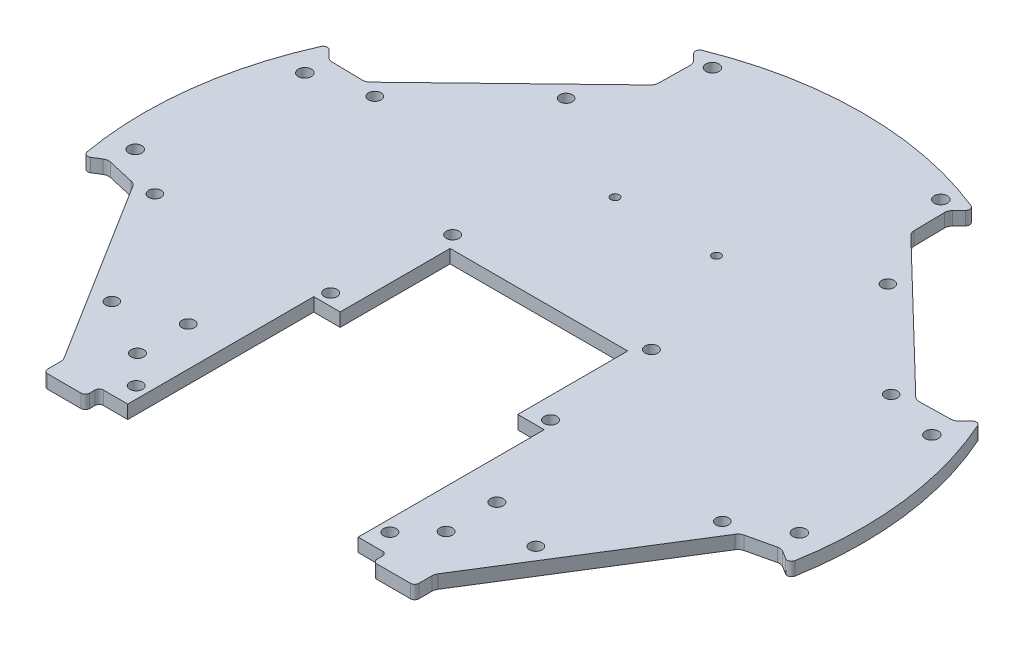
SolidWorks part; units mm, degrees
note: '?' marks a value the reader was unsure of.
material "6061 Alloy"
ref_plane "Front Plane" through (0, 0, 0) normal (0, 0, 1) x (1, 0, 0)
ref_plane "Top Plane" through (0, 0, 0) normal (0, 1, 0) x (1, 0, 0)
ref_plane "Right Plane" through (0, 0, 0) normal (1, 0, 0) x (0, 0, -1)
sketch "Sketch1" plane through (0, 0, 0) normal (0, 1, 0) x (1, 0, 0)
  line L0 (0, 0) -> (0, -62.55) construction
  line L1 (-83.4462, -16.178) -> (-71.2857, -8.5793) construction
  line L6 (0, 0) -> (-59.046, 61.1439) construction
  line L7 (0, 0) -> (-72.0841, -45.0431) construction
  line L8 (-33.174, 78.2591) -> (-23.2129, 67.9442) construction
  line L9 (-72.0841, -45.0431) -> (-70.388, -43.9833) construction
  line L10 (-70.388, -43.9833) -> (-84.9608, -20.662) construction
  line L11 (-84.9608, -20.662) -> (-72.2401, -12.7132) construction
  line L12 (-72.2401, -12.7132) -> (-43.0945, -59.3558) construction
  line L13 (-43.0945, -59.3558) -> (-55.8152, -67.3046) construction
  line L14 (-55.8152, -67.3046) -> (-70.388, -43.9833) construction
  line L21 (-59.046, 61.1439) -> (-57.6566, 59.7052)
  line L22 (-77.4385, 40.6021) -> (-37.8748, 78.8083) construction
  line L23 (-73.9694, 32.6911) -> (-77.0537, 35.885)
  line L24 (-37.8748, 78.8083) -> (-27.4549, 68.0182) construction
  line L25 (-27.4549, 68.0182) -> (-67.0186, 29.812) construction
  line L26 (-67.0186, 29.812) -> (-77.4385, 40.6021) construction
  line L27 (-43.0945, -64.8266) -> (-34, -64.8266)
  line L33 (-86.5505, -18.1178) -> (-71.2857, -8.5793) construction
  line L34 (0, 0) -> (0, 50000) construction
  line L35 (0, 0) -> (-50000, 0) construction
  line L36 (-57.5543, -62.55) -> (-19.8595, -62.55) construction
  line L38 (-67.0927, 25.57) -> (-79.5965, 38.5181) construction
  line L39 (-54.9774, -64.8266) -> (0, -64.8266) construction
  line L40 (-35.7168, 80.8923) -> (-23.2129, 67.9442) construction
  line L41 (-38.9606, -60.3102) -> (-54.2255, -69.8488) construction
  line L42 (-34, -62.55) -> (-19.8595, -62.55) construction
  line L43 (-43.0945, -64.8266) -> (-43.0945, -58.4123) construction
  line L45 (73.9694, 32.6911) -> (77.0537, 35.885)
  line L46 (-71.2857, -8.5793) -> (-38.9606, -60.3102) construction
  line L47 (83.4462, -16.178) -> (79.6809, -13.8252)
  line L48 (69.4846, -16.1792) -> (43.8945, -57.132)
  line L50 (43.0945, -64.8266) -> (34, -64.8266)
  line L51 (34, -62.55) -> (34, -64.8266)
  line L52 (0, 0) -> (72.0841, -45.0431) construction
  line L53 (0, 0) -> (59.046, 61.1439) construction
  line L54 (-30.0897, 75.0653) -> (-30.2847, 63.8954)
  line L55 (-62.7996, 32.4961) -> (-30.2847, 63.8954)
  line L56 (-30.0897, 75.0653) -> (-33.174, 78.2591)
  line L57 (73.9694, 32.6911) -> (77.0537, 35.885)
  line L58 (30.0897, 75.0653) -> (33.174, 78.2591)
  line L59 (-34, -62.55) -> (-34, -61.55)
  line L60 (62.7996, 32.4961) -> (30.2847, 63.8954)
  line L61 (-73.9694, 32.6911) -> (-62.7996, 32.4961)
  line L62 (-77.0537, 35.885) -> (-67.0927, 25.57) construction
  line L63 (-83.4462, -16.178) -> (-79.6809, -13.8252)
  line L64 (-79.6809, -13.8252) -> (-69.4846, -16.1792)
  line L65 (-69.4846, -16.1792) -> (-43.8945, -57.132)
  line L66 (-27.4549, 68.0182) -> (-23.2129, 67.9442) construction
  line L67 (-72.2401, -12.7132) -> (-71.2857, -8.5793) construction
  line L68 (30.0897, 75.0653) -> (30.2847, 63.8954)
  line L69 (73.9694, 32.6911) -> (62.7996, 32.4961)
  line L70 (-34, -62.55) -> (-34, -64.8266)
  line L71 (79.6809, -13.8252) -> (69.4846, -16.1792)
  line L72 (-34, -61.55) -> (-20, -61.55)
  line L73 (-20, -61.55) -> (-19.8595, -62.55)
  line L74 (-19.8595, -62.55) -> (19.8595, -62.55)
  line L75 (20, -61.55) -> (19.8595, -62.55)
  line L76 (34, -61.55) -> (20, -61.55)
  line L77 (34, -62.55) -> (34, -61.55)
  line L78 (-43.0945, -64.8266) -> (-43.8945, -64.8266)
  line L79 (-19.8595, -62.55) -> (0, -62.55) construction
  line L80 (-19.8595, -62.55) -> (34, -62.55) construction
  line L81 (-43.8945, -64.8266) -> (-43.8945, -57.132)
  line L82 (-43.0945, -58.4123) -> (-43.8945, -57.132) construction
  line L83 (43.8945, -64.8266) -> (43.8945, -57.132)
  line L84 (43.0945, -64.8266) -> (43.8945, -64.8266)
  line L97 (-23.2129, 67.9442) -> (-67.0927, 25.57) construction
  circle A0 centre (0, 0) radius 85 construction
  circle A1 centre (0, 0) radius 90 construction
  arc A51 (-77.0537, 35.885) -> (-83.4462, -16.178) centre (0, 0) ccw
  arc A52 (77.0537, 35.885) -> (83.4462, -16.178) centre (0, 0) cw
  arc A54 (-33.174, 78.2591) -> (33.174, 78.2591) centre (0, 0) cw
  point P29 (-31.6318, 76.6622)
  point P33 (-47.2368, 48.9151)
  point P34 (31.6318, 76.6622)
  point P35 (-57.6673, -36.0345)
  point P85 (-57.6566, 59.7052)
  dimension "D2" = 58
  dimension "D10" = 82
  dimension "D12" = 170
  dimension "D14" = 34
  dimension "D13" = 1
  dimension "D15" = 3
  dimension "D3" = 180
  dimension "D4" = 64.8266
  dimension "D5" = 44
  dimension "D6" = 15
  dimension "D7" = 55
  dimension "D8" = 62.55
  dimension "D9" = 2
  dimension "D11" = 2
  dimension "D16" = 7
  dimension "D17" = 7
  dimension "D18" = 0.5
  dimension "D19" = 1
  dimension "D20" = 14
  dimension "D21" = 0.8
extrude "Boss-Extrude4" add sketch "Sketch1" along normal mid plane 3.175
ref_point "Rear_Axle_Center (L)"
ref_axis "Rear_Axle_Proj (L)" through (46.5421, 0, -48.1958) along (0, 1, 0)?
ref_point "Front_Axle_Center (L)"
ref_axis "Front_Axle_Proj (L)" through (57.2432, 0, 35.7696) along (0, 1, 0)?
ref_point "Front_Axle_Center (R)"
ref_axis "Front_Axle_Proj (R)" through (-57.2432, 0, 35.7696) along (0, 1, 0)?
ref_point "Read_Axle_Center (R)"
ref_axis "Rear_Axle_Proj (R)" through (-46.5421, 0, -48.1958) along (0, 1, 0)?
sketch "Sketch17" plane through (0, 1.5875, 0) normal (0, 1, 0) x (1, 0, 0)
  line L0 (0, -57.55) -> (0, -62.55) construction
  line L1 (-19.8595, -62.55) -> (19.8595, -62.55) construction
  circle A0 centre (0, -57.55) radius 8.5
  dimension "D1" = 17
  dimension "D2" = 5
extrude "Boss-Extrude5" [suppressed] add sketch "Sketch17" against normal up to surface (3.175 mm away)
ref_plane "Plane1" through (0, 0, 10) normal (0, 0, 1) x (1, 0, 0)
hole_wizard "M3 Clearance Hole3" positions "Sketch18" profile "Sketch19" hole size "M3" standard "ANSI Metric" end condition through all
sketch "Sketch18" plane through (0, -1.5875, 0) normal (0, -1, 0) x (-1, 0, 0)
  line L0 (-36.5, -50) -> (-36.5, -38) construction
  line L3 (0, 0) -> (0, -38) construction
  line L4 (36.5, -50) -> (36.5, -38) construction
  line L6 (0, -38) -> (36.5, -38) construction
  line L8 (0, -38) -> (-36.5, -38) construction
  line L9 (-36.5, -44) -> (36.5, -44) construction
  line L10 (0, -44) -> (0, 0) construction
  point P1 (36.5, -50)
  point P3 (36.5, -38)
  point P5 (-36.5, -50)
  point P33 (-36.5, -38)
  dimension "D1" = 12
  dimension "D2" = 73
  dimension "D4" = 38
sketch "Sketch19" plane through (-36.5, -1.5875, 50) normal (1, 0, 0) x (0, 0, -1)
  line L0 (0, 0) -> (0, 3.175)
  line L1 (0, 3.175) -> (1.5, 3.175)
  line L2 (1.5, 3.175) -> (1.5, 0)
  line L5 (1.5, 0) -> (0, 0)
  line L11 (0, -6.35) -> (0, 107.95) construction
  dimension "Thru Hole Dia." = 3
  dimension "Thru Hole Depth" = 3.175
hole_wizard "M3 Clearance Hole1" positions "Sketch11" profile "Sketch12" hole size "M3" standard "ANSI Metric" end condition through all
sketch "Sketch11" plane through (0, 1.5875, 0) normal (0, 1, 0) x (1, 0, 0)
  line L0 (83.4462, -16.178) -> (79.6809, -13.8252) construction
  line L2 (73.9694, 32.6911) -> (77.0537, 35.885) construction
  line L4 (-73.9694, 32.6911) -> (-77.0537, 35.885) construction
  line L6 (0, 0) -> (0, -50000) construction
  line L7 (78.4111, 9.6277) -> (84.3664, 10.3589) construction
  line L10 (74.155, 27.2403) -> (78.5423, -8.4914) construction
  line L12 (78.4111, 9.6277) -> (76.3487, 9.3744) construction
  arc A7 (77.964, -12.7523) -> (72.563, 31.2347) centre (0, 0) ccw construction
  arc A13 (-77.964, -12.7523) -> (-72.563, 31.2347) centre (0, 0) cw construction
  arc A17 (83.4462, -16.178) -> (77.0537, 35.885) centre (0, 0) ccw construction
  point P34 (78.5423, -8.4914)
  point P66 (74.155, 27.2403)
  point P70 (-74.155, 27.2403)
  point P71 (-78.5423, -8.4914)
  dimension "D1" = 6
  dimension "D2" = 36
sketch "Sketch12" plane through (-78.5423, 1.5875, 8.4914) normal (1, 0, 0) x (0, 0, 1)
  line L0 (0, 0) -> (0, 3.175)
  line L1 (0, 3.175) -> (1.55, 3.175)
  line L2 (1.55, 3.175) -> (1.55, 0)
  line L5 (1.55, 0) -> (0, 0)
  line L11 (0, -6.35) -> (0, 107.95) construction
  dimension "Thru Hole Dia." = 3.1
  dimension "Thru Hole Depth" = 3.175
hole_wizard "M3 Clearance Hole4" positions "Sketch9" profile "Sketch10" hole size "M3" standard "ANSI Metric" end condition through all
sketch "Sketch9" plane through (0, -1.5875, 0) normal (0, -1, 0) x (-1, 0, 0)
  line L0 (0, 0) -> (0, 63.4318) construction
  line L1 (-38.0437, 52.9272) -> (38.0437, 52.9272) construction
  line L3 (61.0625, 30.6981) -> (-61.0625, 30.6981) construction
  line L4 (-67.0993, -15.2789) -> (67.0993, -15.2789) construction
  line L5 (50.1419, -42.4164) -> (-50.1419, -42.4164) construction
  line L6 (-61.0625, 30.6981) -> (-38.0437, 52.9272) construction
  line L7 (38.0437, 52.9272) -> (61.0625, 30.6981) construction
  line L8 (67.0993, -15.2789) -> (50.1419, -42.4164) construction
  line L9 (-50.1419, -42.4164) -> (-67.0993, -15.2789) construction
  line L10 (0, 0) -> (-44.8055, 46.3974) construction
  line L11 (0, 0) -> (44.8055, 46.3974) construction
  line L12 (0, 0) -> (-96.9468, 0) construction
  line L14 (-55.1231, -34.4448) -> (0, 0) construction
  line L15 (0, 0) -> (55.1231, -34.4448) construction
  line L18 (-69.4846, -16.1792) -> (-43.8945, -57.132) construction
  line L19 (-62.7996, 32.4961) -> (-30.2847, 63.8954) construction
  point P0 (-67.0993, -15.2789)
  point P2 (-50.1419, -42.4164)
  point P9 (-61.0625, 30.6981)
  point P11 (-38.0437, 52.9272)
  point P30 (50.1419, -42.4164)
  point P31 (67.0993, -15.2789)
  point P32 (38.0437, 52.9272)
  point P33 (61.0625, 30.6981)
  dimension "D9" = 46
  dimension "D10" = 46
  dimension "D11" = 32
  dimension "D12" = 32
  dimension "D7" = 58
  dimension "D5" = 32
  dimension "D6" = 2.5
  dimension "D8" = 9.4
  dimension "D2" = 44
  dimension "D3" = 32
  dimension "D4" = 2.5
  dimension "D13" = 9.4
sketch "Sketch10" plane through (67.0993, -1.5875, 15.2789) normal (1, 0, 0) x (0, 0, -1)
  line L0 (0, 0) -> (0, 3.175)
  line L1 (0, 3.175) -> (1.475, 3.175)
  line L2 (1.475, 3.175) -> (1.475, 0)
  line L5 (1.475, 0) -> (0, 0)
  line L11 (0, -6.35) -> (0, 107.95) construction
  dimension "Thru Hole Dia." = 2.95
  dimension "Thru Hole Depth" = 3.175
hole_wizard "M3 Clearance Hole2" positions "Sketch13" profile "Sketch14" hole size "M3" standard "ANSI Metric" end condition through all
sketch "Sketch13" plane through (0, 1.5875, 0) normal (0, 1, 0) x (1, 0, 0)
  line L0 (0, 0) -> (0, 85) construction
  line L2 (-24, 47) -> (-24, 81) construction
  line L3 (-24, 47) -> (24, 47) construction
  line L4 (-24, 81) -> (24, 81) construction
  line L5 (24, 47) -> (24, 81) construction
  line L6 (-24, 47) -> (24, 81) construction
  line L7 (-24, 81) -> (24, 47) construction
  line L8 (-38.0437, 52.9272) -> (-61.0625, 30.6981) construction
  line L10 (-36.307, 51.1289) -> (-59.3259, 28.8998) construction
  line L11 (-16.3488, 39.8187) -> (-31.6313, 55.6441) construction
  line L12 (-16.3488, 39.8187) -> (-48.7191, 8.559) construction
  line L13 (-31.6313, 55.6441) -> (-64.0016, 24.3845) construction
  line L14 (-48.7191, 8.559) -> (-64.0016, 24.3845) construction
  line L15 (-16.3488, 39.8187) -> (-64.0016, 24.3845) construction
  line L16 (-31.6313, 55.6441) -> (-48.7191, 8.559) construction
  line L17 (-49.5531, 41.8127) -> (-40.1752, 32.1016) construction
  line L18 (-27, 76.4978) -> (-27, 80.5978) construction
  arc A0 (33.174, 78.2591) -> (-33.174, 78.2591) centre (0, 0) ccw construction
  circle A1 centre (-16.2162, 44) radius 3 construction
  circle A2 centre (-27, 76.4978) radius 3 construction
  point P65 (0, 64)
  point P181 (-27, 76.4978)
  point P184 (27, 76.4978)
  dimension "D7" = 6
  dimension "D1" = 48
  dimension "D2" = 34
  dimension "D3" = 4
  dimension "D5" = 45
  dimension "D6" = 22
  dimension "D8" = 4.1
  dimension "D4" = 2.5
sketch "Sketch14" plane through (27, 1.5875, -76.4978) normal (1, 0, 0) x (0, 0, 1)
  line L0 (0, 0) -> (0, 3.175)
  line L1 (0, 3.175) -> (1.55, 3.175)
  line L2 (1.55, 3.175) -> (1.55, 0)
  line L5 (1.55, 0) -> (0, 0)
  line L11 (0, -6.35) -> (0, 107.95) construction
  dimension "Thru Hole Dia." = 3.1
  dimension "Thru Hole Depth" = 3.175
hole_wizard "M3 Clearance Hole5" [suppressed] positions "Sketch24" profile "Sketch25" hole size "M3" standard "ANSI Metric"
sketch "Sketch24" plane through (0, 1.5875, 0) normal (0, 1, 0) x (1, 0, 0)
  line L1 (-11, -4.4) -> (11, -4.4) construction
  line L2 (11, -4.4) -> (11, -36.4) construction
  line L3 (11, -36.4) -> (-11, -36.4) construction
  line L4 (-11, -36.4) -> (-11, -4.4) construction
  line L7 (-11, 37.6) -> (11, 37.6) construction
  line L8 (0, -4.4) -> (0, 0) construction
  line L9 (0, 0) -> (0, 37.6) construction
  point P8 (-11, -4.4)
  point P10 (11, -4.4)
  point P12 (11, -36.4)
  point P14 (-11, -36.4)
  point P42 (-11, 37.6)
  point P45 (11, 37.6)
  dimension "D1" = 22
  dimension "D2" = 32
  dimension "D3" = 4.4
  dimension "D4" = 42
sketch "Sketch25" plane through (-11, 1.5875, 4.4) normal (1, 0, 0) x (0, 0, 1)
  line L0 (0, 0) -> (0, 3.175)
  line L1 (0, 3.175) -> (1.5, 3.175)
  line L2 (1.5, 3.175) -> (1.5, 0)
  line L5 (1.5, 0) -> (0, 0)
  line L11 (0, -6.35) -> (0, 107.95) construction
  dimension "Thru Hole Dia." = 3
  dimension "Thru Hole Depth" = 3.175
sketch "Sketch20" plane through (0, 1.5875, 0) normal (0, 1, 0) x (1, 0, 0)
  line L0 (-16.1485, 44) -> (-16.1485, 39) construction
  line L1 (-14.6485, 44) -> (-14.6485, 39)
  line L2 (-17.6485, 44) -> (-17.6485, 39)
  line L3 (0, 0) -> (0, 85) construction
  line L5 (16.1485, 44) -> (16.1485, 39) construction
  line L6 (14.6485, 44) -> (14.6485, 39)
  line L7 (17.6485, 44) -> (17.6485, 39)
  arc A0 (-14.6485, 44) -> (-17.6485, 44) centre (-16.1485, 44) ccw
  arc A1 (-17.6485, 39) -> (-14.6485, 39) centre (-16.1485, 39) ccw
  arc A5 (33.174, 78.2591) -> (-33.174, 78.2591) centre (0, 0) ccw construction
  arc A7 (14.6485, 44) -> (17.6485, 44) centre (16.1485, 44) cw
  arc A8 (17.6485, 39) -> (14.6485, 39) centre (16.1485, 39) cw
  point P2 (-16.1485, 41.5)
  point P16 (16.1485, 41.5)
  dimension "D1" = 44
  dimension "D2" = 3
  dimension "D3" = 5
  dimension "D4" = 16.1485
extrude "Cut-Extrude1" [suppressed] cut sketch "Sketch20" against normal through all
sketch "Sketch22" plane through (0, 1.5875, 0) normal (0, 1, 0) x (1, 0, 0)
  line L0 (-56.6896, -36.6556) -> (-58.0464, -37.5035) construction
  line L1 (-69.4846, -16.1792) -> (-43.8945, -57.132) construction
  line L3 (30.2452, 66.1578) -> (65.062, 32.5356)
  line L4 (71.6894, -15.6702) -> (43.8945, -60.1514)
  line L5 (-19.8595, -62.55) -> (19.8595, -62.55) construction
  line L6 (-43.8945, -64.8266) -> (-43.8945, -57.132) construction
  line L28 (-30.2452, 66.1578) -> (-65.062, 32.5356)
  line L29 (-71.6894, -15.6702) -> (-43.8945, -60.1514)
  line L30 (-79.6809, -13.8252) -> (-69.4846, -16.1792) construction
  line L31 (0, 85) -> (0, -62.55) construction
  line L32 (-46.5421, 48.1958) -> (-47.6536, 49.3467) construction
  line L37 (-20, -61.55) -> (-19.8595, -62.55)
  line L38 (-20, -61.55) -> (-19.8595, -62.55)
  line L40 (-43.8945, -57.132) -> (-43.8945, -64.8266)
  line L41 (-43.8945, -57.132) -> (-43.8945, -64.8266)
  line L43 (43.8945, -64.8266) -> (43.8945, -57.132)
  line L44 (43.8945, -64.8266) -> (43.8945, -57.132)
  line L56 (-19.8595, -62.55) -> (19.8595, -62.55)
  line L58 (19.8595, -62.55) -> (20, -61.55)
  line L59 (20, -61.55) -> (34, -61.55)
  line L60 (34, -61.55) -> (34, -64.8266)
  line L61 (34, -64.8266) -> (43.8945, -64.8266)
  line L63 (43.8945, -57.132) -> (69.4846, -16.1792)
  line L64 (69.4846, -16.1792) -> (79.6809, -13.8252)
  line L65 (79.6809, -13.8252) -> (83.4462, -16.178)
  line L66 (77.0537, 35.885) -> (73.9694, 32.6911)
  line L67 (73.9694, 32.6911) -> (62.7996, 32.4961)
  line L68 (62.7996, 32.4961) -> (30.2847, 63.8954)
  line L69 (30.2847, 63.8954) -> (30.0897, 75.0653)
  line L70 (30.0897, 75.0653) -> (33.174, 78.2591)
  line L71 (-33.174, 78.2591) -> (-30.0897, 75.0653)
  line L72 (-30.0897, 75.0653) -> (-30.2847, 63.8954)
  line L73 (-30.2847, 63.8954) -> (-62.7996, 32.4961)
  line L74 (-62.7996, 32.4961) -> (-73.9694, 32.6911)
  line L75 (-73.9694, 32.6911) -> (-77.0537, 35.885)
  line L76 (-83.4462, -16.178) -> (-79.6809, -13.8252)
  line L77 (-79.6809, -13.8252) -> (-69.4846, -16.1792)
  line L78 (-69.4846, -16.1792) -> (-43.8945, -57.132)
  line L80 (-43.8945, -64.8266) -> (-34, -64.8266)
  line L81 (-34, -64.8266) -> (-34, -61.55)
  line L82 (-34, -61.55) -> (-20, -61.55)
  line L84 (-19.8595, -62.55) -> (19.8595, -62.55)
  line L86 (19.8595, -62.55) -> (20, -61.55)
  line L87 (20, -61.55) -> (34, -61.55)
  line L88 (34, -61.55) -> (34, -64.8266)
  line L89 (34, -64.8266) -> (43.8945, -64.8266)
  line L91 (43.8945, -57.132) -> (69.4846, -16.1792)
  line L92 (69.4846, -16.1792) -> (79.6809, -13.8252)
  line L93 (79.6809, -13.8252) -> (83.4462, -16.178)
  line L94 (77.0537, 35.885) -> (73.9694, 32.6911)
  line L95 (73.9694, 32.6911) -> (62.7996, 32.4961)
  line L96 (62.7996, 32.4961) -> (30.2847, 63.8954)
  line L97 (30.2847, 63.8954) -> (30.0897, 75.0653)
  line L98 (30.0897, 75.0653) -> (33.174, 78.2591)
  line L99 (-33.174, 78.2591) -> (-30.0897, 75.0653)
  line L100 (-30.0897, 75.0653) -> (-30.2847, 63.8954)
  line L101 (-30.2847, 63.8954) -> (-62.7996, 32.4961)
  line L102 (-62.7996, 32.4961) -> (-73.9694, 32.6911)
  line L103 (-73.9694, 32.6911) -> (-77.0537, 35.885)
  line L104 (-83.4462, -16.178) -> (-79.6809, -13.8252)
  line L105 (-79.6809, -13.8252) -> (-69.4846, -16.1792)
  line L106 (-69.4846, -16.1792) -> (-43.8945, -57.132)
  line L108 (-43.8945, -64.8266) -> (-34, -64.8266)
  line L109 (-34, -64.8266) -> (-34, -61.55)
  line L110 (-34, -61.55) -> (-20, -61.55)
  arc A9 (83.4462, -16.178) -> (77.0537, 35.885) centre (0, 0) ccw
  arc A10 (33.174, 78.2591) -> (-33.174, 78.2591) centre (0, 0) ccw
  arc A11 (-77.0537, 35.885) -> (-83.4462, -16.178) centre (0, 0) ccw
  arc A13 (83.4462, -16.178) -> (77.0537, 35.885) centre (0, 0) ccw
  arc A14 (33.174, 78.2591) -> (-33.174, 78.2591) centre (0, 0) ccw
  arc A15 (-77.0537, 35.885) -> (-83.4462, -16.178) centre (0, 0) ccw
  dimension "D2" = 1.6
  dimension "D1" = 0
extrude "Boss-Extrude6" add sketch "Sketch22" against normal up to surface (3.175 mm away) up to face at (-27, -1.5875, -74.9478)
fillet "Fillet1" radius 2 14 edges at (-30.0897, 0, -75.0653) (30.0897, 0, -75.0653) (-79.6809, 0, 13.8252) (79.6809, 0, 13.8252) (73.9694, 0, -32.6911) (-73.9694, 0, -32.6911) (65.062, 0, -32.5356) (30.2452, 0, -66.1578) (71.6894, 0, 15.6702) (-71.6894, 0, 15.6702) (-65.062, 0, -32.5356) (-30.2452, 0, -66.1578) (43.8945, 0, 60.1514) (-43.8945, 0, 60.1514)
fillet "Fillet3" radius 1 12 edges at (-77.0537, 0, -35.885) (77.0537, 0, -35.885) (83.4462, 0, 16.178) (34, 0, 64.8266) (-34, 0, 64.8266) (-33.174, 0, -78.2591) (33.174, 0, -78.2591) (-83.4462, 0, 16.178) (34, 0, 61.55) (-34, 0, 61.55) (-43.8945, 0, 64.8266) (43.8945, 0, 64.8266)
sketch "Sketch23" [suppressed] plane through (0, 3.175, 0) normal (0, 1, 0) x (1, 0, 0)
  circle A0 centre (0, -53.55) radius 4.95
  dimension "D1" = 9.9
fillet "Fillet6" radius 0.5 4 edges at (20, 0, 61.55) (19.8595, 0, 62.55) (-20, 0, 61.55) (-19.8595, 0, 62.55)
sketch "Sketch28" plane through (0, 1.5875, 0) normal (0, 1, 0) x (1, 0, 0)
  line L0 (-19.4248, -62.55) -> (19.4248, -62.55) construction
  line L1 (-19.4248, -62.55) -> (19.4248, -62.55) construction
  line L2 (-27.25, -62.55) -> (27.25, -62.55)
  line L3 (-27.25, -62.55) -> (-27.25, -17.55)
  line L4 (27.25, -62.55) -> (27.25, -17.55)
  line L5 (-27.25, -17.55) -> (27.25, -17.55)
  arc A0 (19.4248, -62.55) -> (19.9199, -62.1196) centre (19.4248, -62.05) ccw construction
  point P11 (0, -62.55)
  dimension "D1" = 54.5
  dimension "D2" = 45
extrude "Cut-Extrude4" cut sketch "Sketch28" against normal blind 10
extrude "Cut-Extrude2" [suppressed] cut sketch "Sketch23" against normal through all
sketch "Sketch26" [suppressed] plane through (0, 3.175, 0) normal (0, 1, 0) x (1, 0, 0)
  line L0 (0, 0) -> (0, 50) construction
  line L1 (-92.5, 5) -> (92.5, 5)
  line L2 (-92.5, 5) -> (-92.5, 95)
  line L3 (-92.5, 95) -> (92.5, 95)
  line L4 (92.5, 5) -> (92.5, 95)
  line L5 (-92.5, 5) -> (92.5, 95) construction
  line L6 (-92.5, 95) -> (92.5, 5) construction
  point P0 (0, 50)
  dimension "D1" = 90
  dimension "D2" = 185
  dimension "D3" = 5
extrude "Cut-Extrude3" [suppressed] cut sketch "Sketch26" against normal through all
fillet "Fillet4" [suppressed] radius 5
sketch "Sketch29" plane through (0, 1.5875, 0) normal (0, 1, 0) x (1, 0, 0)
  line L0 (-27.25, -61.55) -> (-27.25, -56.8)
  line L2 (-27.25, -17.55) -> (-27.25, -61.55) construction
  line L3 (-27.25, -56.8) -> (-33.5626, -56.8) construction
  line L4 (-27.25, -56.8) -> (-30, -56.8)
  line L5 (27.25, -56.8) -> (30, -56.8)
  line L6 (27.25, -61.55) -> (27.25, -17.55) construction
  circle A0 centre (30, -56.8) radius 1.5
  circle A1 centre (-30, -56.8) radius 1.5
  dimension "D4" = 3
  dimension "D5" = 3
  dimension "D1" = 4.75
  dimension "D2" = 2.75
  dimension "D3" = 2.75
extrude "Cut-Extrude5" cut sketch "Sketch29" against normal blind 10 contours L4 L3 A1 | L3 L4 A1 | A0 L3 L5 | L3 A0 L5
sketch "Sketch30" plane through (0, 1.5875, 0) normal (0, 1, 0) x (1, 0, 0)
  line L0 (-21, -17.55) -> (21, -17.55)
  line L2 (27.25, -17.55) -> (-27.25, -17.55) construction
  line L3 (-21, -17.55) -> (-21, 8.45)
  line L4 (21, -17.55) -> (21, 8.45)
  line L5 (21, 8.45) -> (-21, 8.45)
  point P5 (0, -17.55)
  dimension "D1" = 42
  dimension "D2" = 26
extrude "Cut-Extrude6" cut sketch "Sketch30" against normal blind 10
sketch "Sketch31" plane through (0, 1.5875, 0) normal (0, 1, 0) x (1, 0, 0)
  line L0 (-21, -17.55) -> (-21, -14.8)
  line L1 (-21, 8.45) -> (-21, -17.55) construction
  line L2 (-21, -14.8) -> (-26, -14.8)
  line L3 (21, -17.55) -> (21, -14.8)
  line L4 (21, -17.55) -> (21, 8.45) construction
  line L5 (21, -14.8) -> (26, -14.8)
  circle A0 centre (-26, -14.8) radius 1.5
  circle A1 centre (26, -14.8) radius 1.5
  dimension "D3" = 3
  dimension "D6" = 3
  dimension "D1" = 2.75
  dimension "D2" = 5
  dimension "D4" = 2.75
  dimension "D5" = 5
extrude "Cut-Extrude7" cut sketch "Sketch31" against normal blind 10
sketch "Sketch34" plane through (0, 1.5875, 0) normal (0, 1, 0) x (1, 0, 0)
  line L0 (-21, 8.45) -> (-12, 8.45) construction
  line L1 (21, 8.45) -> (-21, 8.45) construction
  line L2 (-12, 8.45) -> (-12, 38.45) construction
  line L3 (-12, 38.45) -> (12, 38.45) construction
  line L4 (12, 38.45) -> (12, 8.45) construction
  line L5 (12, 8.45) -> (21, 8.45) construction
  circle A0 centre (-12, 38.45) radius 1
  circle A1 centre (12, 38.45) radius 1
  dimension "D4" = 2
  dimension "D5" = 2
  dimension "D1" = 9
  dimension "D2" = 9
  dimension "D3" = 30
extrude "Cut-Extrude9" cut sketch "Sketch34" against normal blind 10
sketch "Sketch35" plane through (0, 1.5875, 0) normal (0, 1, 0) x (1, 0, 0)
  line L0 (-21, 8.45) -> (-21, 11.55)
  line L1 (-21, 11.55) -> (-23.5, 11.55)
  line L2 (21, 8.45) -> (21, 11.55)
  line L3 (21, 11.55) -> (23.5, 11.55)
  circle A0 centre (-23.5, 11.55) radius 1.5
  circle A1 centre (23.5, 11.55) radius 1.5
  dimension "D5" = 3
  dimension "D6" = 3
  dimension "D1" = 2.5
  dimension "D2" = 3.1
  dimension "D3" = 2.5
  dimension "D4" = 3.1
extrude "Cut-Extrude10" cut sketch "Sketch35" against normal through all
equation "\"D3@Sketch9\"=\"D5@Sketch9\""
equation "\"D4@Sketch9\"=\"D6@Sketch9\""
equation "\"D13@Sketch9\"=\"D8@Sketch9\""
